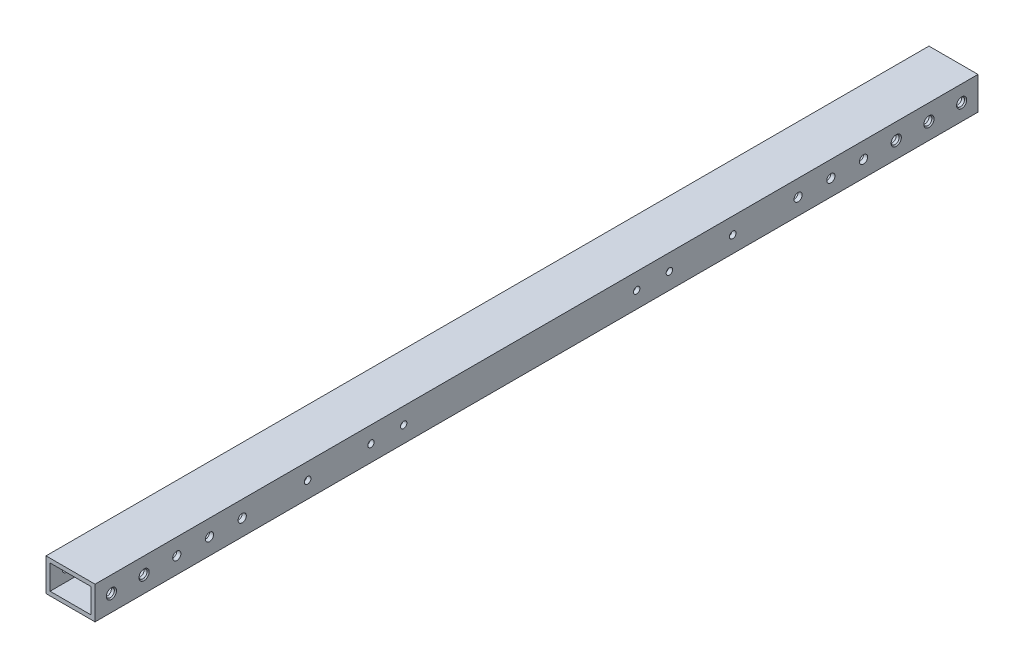
SolidWorks part; units mm, degrees
ref_plane "Front Plane" through (0, 0, 0) normal (0, 0, 1) x (1, 0, 0)
ref_plane "Top Plane" through (0, 0, 0) normal (0, 1, 0) x (1, 0, 0)
ref_plane "Right Plane" through (0, 0, 0) normal (1, 0, 0) x (0, 0, -1)
sketch "Sketch1" plane through (0, 0, 0) normal (0, 0, 1) x (1, 0, 0)
  line L0 (-15.875, 9.525) -> (15.875, 9.525)
  line L2 (-19.05, 12.7) -> (19.05, 12.7)
  line L3 (-19.05, 12.7) -> (-19.05, -12.7)
  line L4 (-19.05, -12.7) -> (19.05, -12.7)
  line L5 (19.05, 12.7) -> (19.05, -12.7)
  line L10 (15.875, 9.525) -> (15.875, -9.525)
  line L11 (-15.875, -9.525) -> (15.875, -9.525)
  line L12 (-15.875, 9.525) -> (-15.875, -9.525)
  point P12 (0, 12.7)
  point P14 (19.05, 0)
  dimension "Wall Thickness" = 3.175
  dimension "Outside Width" = 38.1
  dimension "Outside Height" = 25.4
  dimension "Inside Height" = 19.05
  dimension "Inside Width" = 31.75
sketch "Sketch2" plane through (0, 0, 0) normal (1, 0, 0) x (0, 0, -1)
  line L0 (342.9, 0) -> (-342.9, 0)
  point P4 (0, 0)
  point P7 (-342.9, 0)
  point P10 (342.9, 0)
  dimension "Length" = 685.8
sketch "Sketch3" plane through (0, 0, 0) normal (0, 0, 1) x (1, 0, 0)
  line L21 (19.05, 12.7) -> (-19.05, 12.7)
  line L22 (19.05, -12.7) -> (19.05, 12.7)
  line L23 (-19.05, -12.7) -> (19.05, -12.7)
  line L24 (-19.05, 12.7) -> (-19.05, -12.7)
  line L25 (19.05, 12.7) -> (-19.05, 12.7)
  line L26 (19.05, -12.7) -> (19.05, 12.7)
  line L27 (-19.05, -12.7) -> (19.05, -12.7)
  line L28 (-19.05, 12.7) -> (-19.05, -12.7)
  line L29 (15.875, 9.525) -> (-15.875, 9.525)
  line L30 (15.875, -9.525) -> (15.875, 9.525)
  line L31 (-15.875, -9.525) -> (15.875, -9.525)
  line L32 (-15.875, 9.525) -> (-15.875, -9.525)
  line L33 (15.875, 9.525) -> (-15.875, 9.525)
  line L34 (15.875, -9.525) -> (15.875, 9.525)
  line L35 (-15.875, -9.525) -> (15.875, -9.525)
  line L36 (-15.875, 9.525) -> (-15.875, -9.525)
  dimension "D1" = 0
  dimension "D2" = 0
extrude "Boss-Extrude1" add sketch "Sketch3" along normal up to vertex (342.9 mm away) and the other way up to vertex (342.9 mm away) up to point (0, 0, 342.9) other way up to point (0, 0, -342.9)
sketch "Drawing Reference" plane through (0, 0, 0) normal (1, 0, 0) x (0, 0, -1)
  line L0 (-342.9, 0) -> (342.9, 0) construction
  line L1 (0, -12.7) -> (0, 12.7) construction
  line L2 (-342.9, -12.7) -> (342.9, -12.7) construction
  line L5 (-342.9, 12.7) -> (342.9, 12.7) construction
  point P7 (-315.468, 0)
  point P8 (315.468, 0)
  dimension "D1" = 27.432
sketch "Sketch4" plane through (-19.05, 0, 0) normal (-1, 0, 0) x (0, 0, 1)
  line L0 (-342.9, 0) -> (-330.2, 0)
  line L1 (-342.9, 12.7) -> (-342.9, -12.7) construction
  line L2 (-330.2, 0) -> (-304.8, 0)
  line L3 (-304.8, 0) -> (-279.4, 0)
  line L4 (-279.4, 0) -> (-254, 0)
  line L5 (-254, 0) -> (-228.6, 0)
  line L6 (-228.6, 0) -> (-203.2, 0)
  line L7 (342.9, 0) -> (330.2, 0)
  line L8 (342.9, 12.7) -> (342.9, -12.7) construction
  line L9 (330.2, 0) -> (304.8, 0)
  line L10 (304.8, 0) -> (279.4, 0)
  line L11 (279.4, 0) -> (254, 0)
  line L12 (254, 0) -> (228.6, 0)
hole_wizard "1/4 (0.25) Diameter Hole2" positions "Sketch7" profile "Sketch8" hole size "1/4" standard "ANSI Inch" end condition through all
sketch "Sketch7" plane through (-19.05, 0, 0) normal (-1, 0, 0) x (0, 0, 1)
  point P0 (-330.2, 0)
  point P3 (-304.8, 0)
  point P7 (330.2, 0)
  point P11 (-279.4, 0)
  point P14 (304.8, 0)
sketch "Sketch8" plane through (-19.05, 0, -330.2) normal (0, 1, 0) x (0, 0, 1)
  line L0 (0, 0) -> (0, 38.1)
  line L1 (0, 38.1) -> (3.9624, 38.1)
  line L2 (3.175, 37.1942) -> (3.175, 0)
  line L5 (3.175, 0) -> (0, 0)
  line L7 (3.9624, 38.1) -> (3.175, 37.1942)
  line L8 (-3.9624, 38.1) -> (-3.175, 37.1942) construction
  line L11 (0, -6.35) -> (0, 107.95) construction
  dimension "Thru Hole Dia." = 6.35
  dimension "Thru Hole Depth" = 38.1
  dimension "Far C'Sink Dia." = 7.9248
  dimension "Far C'Sink Angle" = 82
hole_wizard "1/4 (0.25) Diameter Hole3" positions "Sketch9" profile "Sketch10" hole size "1/4" standard "ANSI Inch" end condition through all
sketch "Sketch9" plane through (19.05, 0, 0) normal (1, 0, 0) x (0, 0, -1)
  point P0 (-279.4, 0)
  point P3 (-254, 0)
  point P6 (-228.6, 0)
  point P9 (254, 0)
  point P12 (228.6, 0)
  point P15 (203.2, 0)
sketch "Sketch10" plane through (19.05, 0, 279.4) normal (0, 1, 0) x (0, 0, -1)
  line L0 (0, 0) -> (0, 38.1)
  line L1 (0, 38.1) -> (3.175, 38.1)
  line L2 (3.175, 38.1) -> (3.175, 0)
  line L5 (3.175, 0) -> (0, 0)
  line L11 (0, -6.35) -> (0, 107.95) construction
  dimension "Thru Hole Dia." = 6.35
  dimension "Thru Hole Depth" = 38.1
hole_wizard "13/64 (0.20313) Diameter Hole1" positions "Sketch11" profile "Sketch12" hole size "13/64" standard "ANSI Inch" end condition through all
sketch "Sketch11" plane through (19.05, 0, 0) normal (1, 0, 0) x (0, 0, -1)
  point P0 (152.4, 0)
  point P3 (-177.8, 0)
sketch "Sketch12" plane through (19.05, 0, -152.4) normal (0, 1, 0) x (0, 0, -1)
  line L0 (0, 0) -> (0, 38.1)
  line L1 (0, 38.1) -> (2.5798, 38.1)
  line L2 (2.5798, 38.1) -> (2.5798, 0)
  line L5 (2.5798, 0) -> (0, 0)
  line L11 (0, -6.35) -> (0, 107.95) construction
  dimension "Thru Hole Dia." = 5.1595
  dimension "Thru Hole Depth" = 38.1
sketch "Sketch13" plane through (19.05, 0, 0) normal (1, 0, 0) x (0, 0, -1)
  line L0 (-103.1875, 0) -> (-128.5875, 0)
  line L1 (77.7875, 0) -> (103.1875, 0)
hole_wizard "#10 Clearance Hole1" positions "Sketch14" profile "Sketch15" hole size "#10" standard "ANSI Inch" end condition through all
sketch "Sketch14" plane through (19.05, 0, 0) normal (1, 0, 0) x (0, 0, -1)
  point P0 (-128.5875, 0)
  point P3 (-103.1875, 0)
  point P7 (77.7875, 0)
  point P10 (103.1875, 0)
sketch "Sketch15" plane through (19.05, 0, 128.5875) normal (0, 1, 0) x (0, 0, -1)
  line L0 (0, 0) -> (0, 38.1)
  line L1 (0, 38.1) -> (2.4892, 38.1)
  line L2 (2.4892, 38.1) -> (2.4892, 0)
  line L5 (2.4892, 0) -> (0, 0)
  line L11 (0, -6.35) -> (0, 107.95) construction
  dimension "Thru Hole Dia." = 4.9784
  dimension "Thru Hole Depth" = 38.1
equation "\"D1@Drawing Reference\"=\"Outside Width@Sketch1\" * 0.72"
